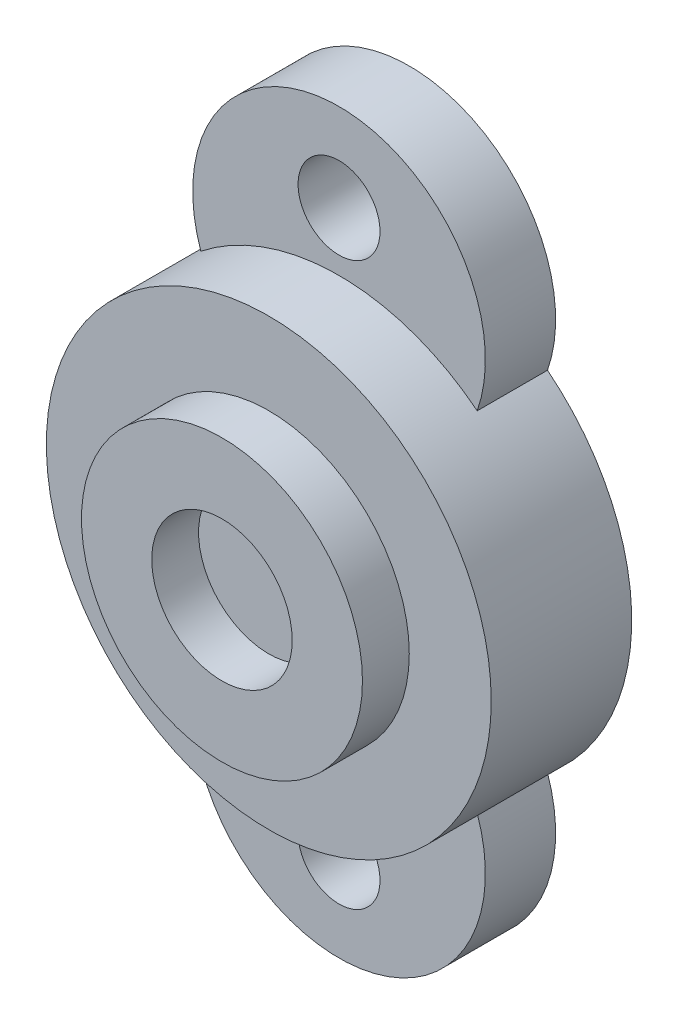
SolidWorks part; units mm, degrees
note: The reader was unsure of these and kept them because the rebuilt part matched: shared geometry of "Sketch1<3>".
material "7079 Alloy"
ref_plane "Front" through (0, 0, 0) normal (0, 0, 1) x (1, 0, 0)
ref_plane "Top" through (0, 0, 0) normal (0, 1, 0) x (1, 0, 0)
ref_plane "Right" through (0, 0, 0) normal (1, 0, 0) x (0, 0, -1)
sketch "Sketch1" plane through (0, 0, 0) normal (0, 0, 1) x (1, 0, 0)
  circle A0 centre (0, 0) radius 6
  circle A1 centre (0, 0) radius 19
  arc A2 (11.8044, 14.8882) -> (-11.8044, 14.8882) centre (0, 19) ccw
  arc A3 (-11.8044, -14.8882) -> (11.8044, -14.8882) centre (0, -19) ccw
  circle A4 centre (0, -24) radius 3.5
  circle A5 centre (0, 24) radius 3.5
  circle A6 centre (0, 0) radius 12
  dimension "D1" = 24
extrude "Extrude1" add sketch "Sketch1" along normal blind 6
extrude "Extrude2" add sketch "Sketch1<3>" along normal blind 16 contours A6 A0
sketch "Sketch1<3>" plane through (0, 0, 0) normal (0, 0, 1) x (1, 0, 0) same geometry as "Sketch1"
sketch "Sketch2" plane through (0, 0, 6) normal (0, 0, 1) x (1, 0, 0)
  circle A0 centre (0, 0) radius 19
extrude "Extrude3" add sketch "Sketch2" along normal blind 6
